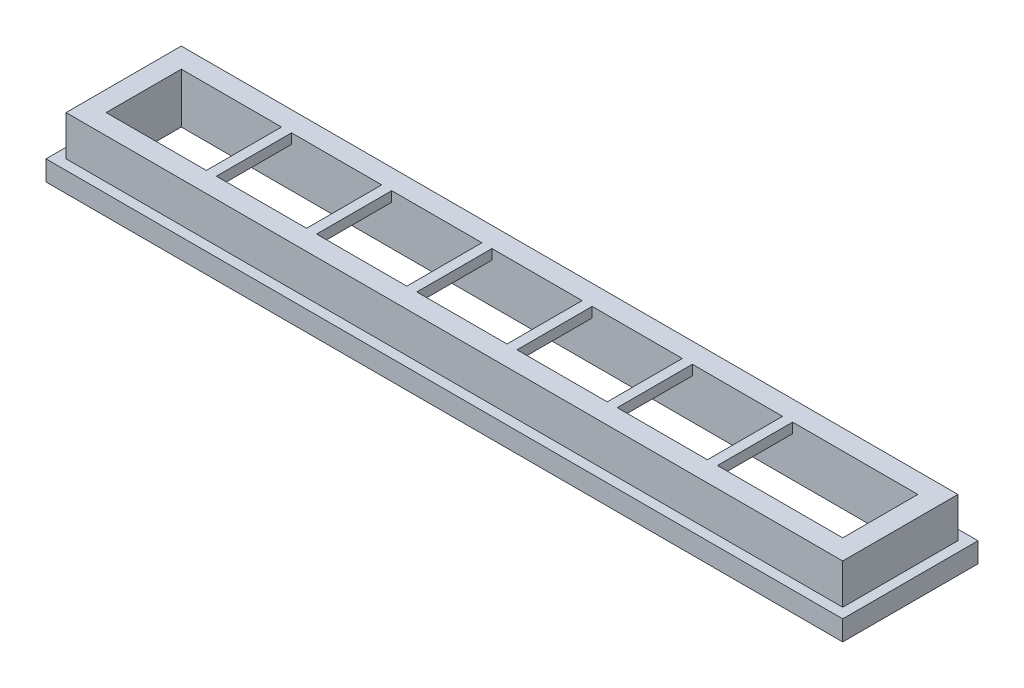
SolidWorks part; units mm, degrees
ref_plane "Ebene vorne" through (0, 0, 0) normal (0, 0, 1) x (1, 0, 0)
ref_plane "Ebene oben" through (0, 0, 0) normal (0, 1, 0) x (1, 0, 0)
ref_plane "Ebene rechts" through (0, 0, 0) normal (1, 0, 0) x (0, 0, -1)
sketch "Skizze1" plane through (0, 0, 0) normal (0, 1, 0) x (1, 0, 0)
  line L1 (-77.5, -11.5) -> (77.5, -11.5)
  line L2 (-77.5, -11.5) -> (-77.5, 11.5)
  line L3 (-77.5, 11.5) -> (77.5, 11.5)
  line L4 (77.5, -11.5) -> (77.5, 11.5)
  line L5 (-77.5, -11.5) -> (77.5, 11.5) construction
  line L6 (-77.5, 11.5) -> (77.5, -11.5) construction
  line L7 (-73.5, -7.5) -> (73.5, -7.5)
  line L8 (-73.5, -7.5) -> (-73.5, 7.5)
  line L9 (-73.5, 7.5) -> (73.5, 7.5)
  line L10 (73.5, -7.5) -> (73.5, 7.5)
  line L11 (-73.5, -7.5) -> (73.5, 7.5) construction
  line L12 (-73.5, 7.5) -> (73.5, -7.5) construction
  point P0 (0, 0)
  point P6 (0, 0)
  dimension "D1" = 4
  dimension "D2" = 4
  dimension "D3" = 155
  dimension "D4" = 23
extrude "Aufsatz-Linear austragen1" add sketch "Skizze1" along normal blind 10
sketch "Skizze2" plane through (0, 10, 0) normal (0, 1, 0) x (1, 0, 0)
  line L0 (73.5, 7.5) -> (-73.5, 7.5) construction
  line L1 (-53.5, 7.5) -> (-51.5, 7.5)
  line L2 (-53.5, 7.5) -> (-53.5, -7.5)
  line L3 (-53.5, -7.5) -> (-51.5, -7.5)
  line L4 (-51.5, 7.5) -> (-51.5, -7.5)
  line L5 (-73.5, -7.5) -> (73.5, -7.5) construction
  line L6 (-73.5, 7.5) -> (-73.5, -7.5) construction
  line L7 (-33.5, 7.5) -> (-31.5, 7.5)
  line L8 (-33.5, 7.5) -> (-33.5, -7.5)
  line L9 (-33.5, -7.5) -> (-31.5, -7.5)
  line L10 (-31.5, 7.5) -> (-31.5, -7.5)
  line L11 (-13.5, 7.5) -> (-11.5, 7.5)
  line L12 (-13.5, 7.5) -> (-13.5, -7.5)
  line L13 (-13.5, -7.5) -> (-11.5, -7.5)
  line L14 (-11.5, 7.5) -> (-11.5, -7.5)
  line L15 (6.5, 7.5) -> (8.5, 7.5)
  line L16 (6.5, 7.5) -> (6.5, -7.5)
  line L17 (6.5, -7.5) -> (8.5, -7.5)
  line L18 (8.5, 7.5) -> (8.5, -7.5)
  line L19 (26.5, 7.5) -> (28.5, 7.5)
  line L20 (26.5, 7.5) -> (26.5, -7.5)
  line L21 (26.5, -7.5) -> (28.5, -7.5)
  line L22 (28.5, 7.5) -> (28.5, -7.5)
  line L23 (46.5, 7.5) -> (48.5, 7.5)
  line L24 (46.5, 7.5) -> (46.5, -7.5)
  line L25 (46.5, -7.5) -> (48.5, -7.5)
  line L26 (48.5, 7.5) -> (48.5, -7.5)
  dimension "D1" = 2
  dimension "D2" = 20
  dimension "D4" = 18
  dimension "D3" = 6
extrude "Aufsatz-Linear austragen2" add sketch "Skizze2" against normal blind 2
sketch "Skizze3" plane through (0, 0, 0) normal (0, -1, 0) x (1, 0, 0)
  line L0 (79.5, -13.5) -> (79.5, 13.5)
  line L1 (79.5, 13.5) -> (-79.5, 13.5)
  line L2 (-79.5, 13.5) -> (-79.5, -13.5)
  line L3 (-79.5, -13.5) -> (79.5, -13.5)
  line L4 (77.5, -11.5) -> (77.5, 11.5)
  line L5 (77.5, 11.5) -> (-77.5, 11.5)
  line L6 (-77.5, 11.5) -> (-77.5, -11.5)
  line L7 (-77.5, -11.5) -> (77.5, -11.5)
  line L8 (77.5, -11.5) -> (77.5, 11.5)
  line L9 (77.5, 11.5) -> (-77.5, 11.5)
  line L10 (-77.5, 11.5) -> (-77.5, -11.5)
  line L11 (-77.5, -11.5) -> (77.5, -11.5)
  dimension "D1" = 0
  dimension "D2" = 2
extrude "Aufsatz-Linear austragen3" add sketch "Skizze3" along normal blind 2 and the other way blind 2
